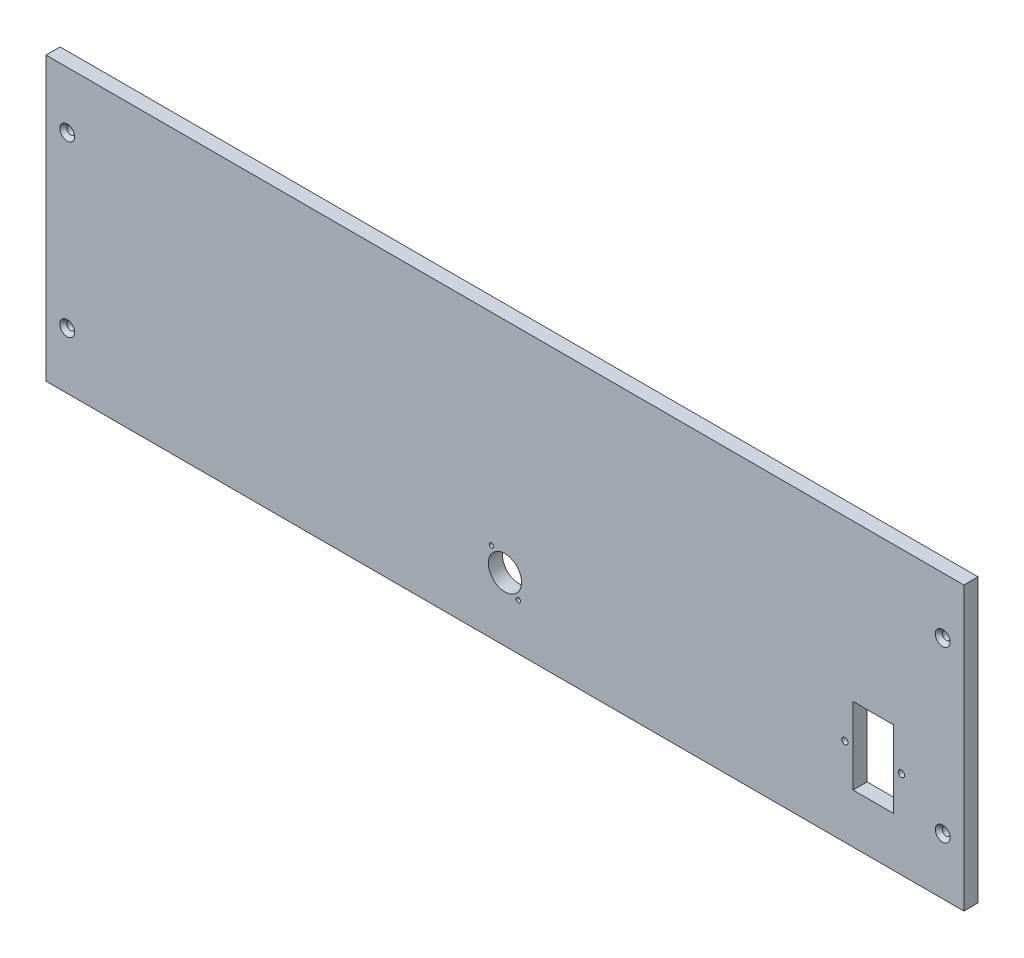
SolidWorks part; units mm, degrees
ref_plane "Plan de face" through (0, 0, 0) normal (0, 0, 1) x (1, 0, 0)
ref_plane "Plan de dessus" through (0, 0, 0) normal (0, 1, 0) x (1, 0, 0)
ref_plane "Plan de droite" through (0, 0, 0) normal (1, 0, 0) x (0, 0, -1)
sketch "Esquisse1" plane through (0, 0, 0) normal (0, 0, 1) x (1, 0, 0)
  line L1 (0, 0) -> (650, 0)
  line L2 (0, 0) -> (0, 200)
  line L3 (0, 200) -> (650, 200)
  line L4 (650, 0) -> (650, 200)
  dimension "D1" = 200
  dimension "D2" = 650
extrude "Boss.-Extru.1" add sketch "Esquisse1" along normal blind 10
sketch "Esquisse2" plane through (0, 0, 10) normal (0, 0, 1) x (1, 0, 0)
  line L0 (0, 200) -> (0, 0) construction
  line L1 (650, 200) -> (0, 200) construction
  line L2 (0, 0) -> (650, 0) construction
  line L3 (650, 0) -> (650, 200) construction
  circle A0 centre (15, 160) radius 2.75
  circle A1 centre (635, 160) radius 2.75
  circle A2 centre (15, 40) radius 2.75
  circle A3 centre (635, 40) radius 2.75
  dimension "D1" = 5.5
  dimension "D2" = 5.5
  dimension "D3" = 5.5
  dimension "D4" = 5.5
  dimension "D5" = 15
  dimension "D6" = 15
  dimension "D7" = 40
  dimension "D8" = 40
  dimension "D9" = 40
  dimension "D10" = 40
  dimension "D11" = 15
  dimension "D12" = 15
extrude "Enlèv. mat.-Extru.1" cut sketch "Esquisse2" against normal blind 10
chamfer "Chanfrein1" distance 2.5 angle 45 4 edges at (17.75, 160, 10) (17.75, 40, 10) (637.75, 40, 10) (637.75, 160, 10)
sketch "Esquisse3" plane through (0, 0, 10) normal (0, 0, 1) x (1, 0, 0)
  line L0 (0, 0) -> (650, 0) construction
  line L1 (334.5004, 33.0006) -> (325, 45)
  line L2 (325, 45) -> (315.4996, 56.9994)
  line L3 (325, 45) -> (265.8175, 45)
  line L4 (325, 45) -> (364.3682, 45)
  line L5 (650, 0) -> (650, 200) construction
  line L6 (571.5, 35) -> (600, 35)
  line L7 (571.5, 35) -> (571.5, 89.3)
  line L8 (571.5, 89.3) -> (600, 89.3)
  line L9 (600, 35) -> (600, 89.3)
  circle A0 centre (325, 45) radius 11.75
  circle A1 centre (315.4996, 56.9994) radius 1.6
  circle A2 centre (334.5004, 33.0006) radius 1.6
  circle A3 centre (565.75, 62.15) radius 2.25
  circle A4 centre (605.75, 62.15) radius 2.25
  point P4 (325, 0)
  point P19 (585.75, 89.3)
  point P20 (571.5, 62.15)
  dimension "D1" = 23.5
  dimension "D4" = 3.2
  dimension "D5" = 3.2
  dimension "D14" = 4.5
  dimension "D15" = 4.5
  dimension "D2" = 0
  dimension "D3" = 45
  dimension "D6" = 30.61
  dimension "D7" = 15.305
  dimension "D8" = 51.63
  dimension "D9" = 180
  dimension "D10" = 51.63
  dimension "D11" = 15.305
  dimension "D12" = 28.5
  dimension "D13" = 54.3
  dimension "D16" = 40
  dimension "D17" = 20
  dimension "D18" = 0
  dimension "D19" = 35
  dimension "D20" = 50
  dimension "D21" = 20
extrude "Enlèv. mat.-Extru.2" cut sketch "Esquisse3" against normal blind 10 contours L3 A0 L1 | L4 A0 L2 | L1 A0 L4 | L2 A0 L3 | A1 | A2 | L6 L9 L8 L7 | A3 | A4 region at (314.1, 57.6764, 10) region at (322.2589, 39.3335, 10) region at (331.8154, 41.7031, 10) region at (335.1774, 34.4002, 10) region at (318.1846, 48.2969, 10) region at (327.7411, 50.6665, 10) region at (585.75, 62.15, 10)
